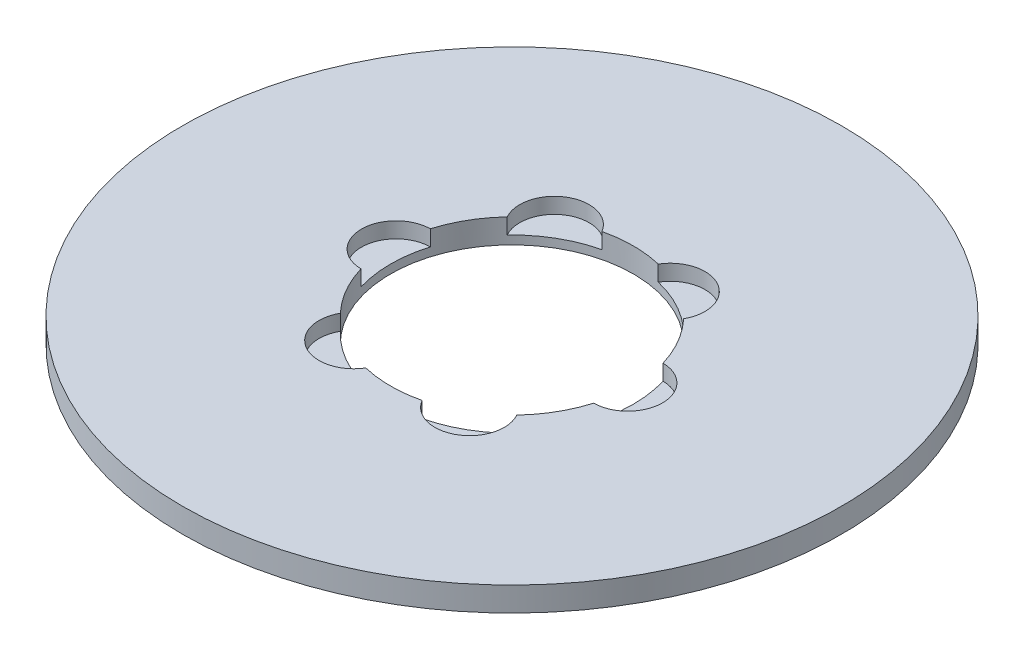
SolidWorks part; units mm, degrees
ref_plane "Front Plane" through (0, 0, 0) normal (0, 0, 1) x (1, 0, 0)
ref_plane "Top Plane" through (0, 0, 0) normal (0, 1, 0) x (1, 0, 0)
ref_plane "Right Plane" through (0, 0, 0) normal (1, 0, 0) x (0, 0, -1)
sketch "Sketch1" plane through (0, 0, 0) normal (0, 1, 0) x (1, 0, 0)
  circle A0 centre (0, 0) radius 95
  dimension "FLANGE_OD" = 190
extrude "Boss-Extrude1" add sketch "Sketch1" along normal blind 7
sketch "Sketch2" plane through (0, 0, 0) normal (0, 1, 0) x (1, 0, 0)
  circle A0 centre (0, 0) radius 35
  dimension "BORE_D" = 70
extrude "Cut-Extrude1" cut sketch "Sketch2" along normal through all
sketch "Sketch3" plane through (0, 7, 0) normal (0, 1, 0) x (1, 0, 0)
  circle A0 centre (0, 0) radius 33.4037 construction
  circle A1 centre (-33.4037, 0) radius 10
  dimension "BOLT_D" = 20
  dimension "BOLT_PCD" = 66.8073
extrude "Cut-Extrude2" cut sketch "Sketch3" against normal blind 4.5189
pattern_circular "CirPattern1" count 6 over 360 about axis through (0, 0, 0) along (0, 1, 0) of "Cut-Extrude2"
